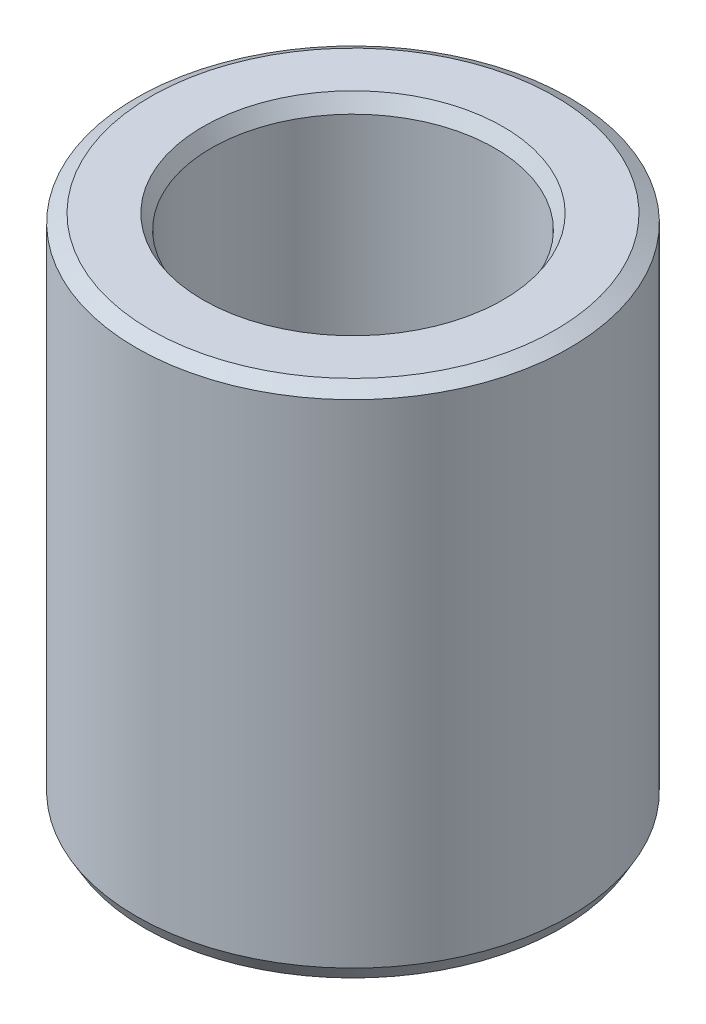
SolidWorks part; units mm, degrees
ref_plane "Front Plane" through (0, 0, 0) normal (0, 0, 1) x (1, 0, 0)
ref_plane "Top Plane" through (0, 0, 0) normal (0, 1, 0) x (1, 0, 0)
ref_plane "Right Plane" through (0, 0, 0) normal (1, 0, 0) x (0, 0, -1)
sketch "Sketch1" plane through (0, 0, 0) normal (0, 1, 0) x (1, 0, 0)
  circle A0 centre (0, 0) radius 55
  dimension "SLEEVE_OD" = 110
extrude "Boss-Extrude1" add sketch "Sketch1" along normal blind 130.7418
sketch "Sketch2" plane through (0, 0, 0) normal (0, 1, 0) x (1, 0, 0)
  circle A0 centre (0, 0) radius 35.981
  dimension "BORE_D" = 71.962
extrude "Cut-Extrude1" cut sketch "Sketch2" along normal through all
chamfer "Chamfer1" distance 2.109 angle 60 4 edges at (0, 130.7418, 35.981) (0, 0, 35.981) (0, 0, 55) (0, 130.7418, 55) first distance on face at (0, 130.7418, 35.981) first distance on face at (0, 0, 35.981) first distance on face at (0, 130.7418, 55)
